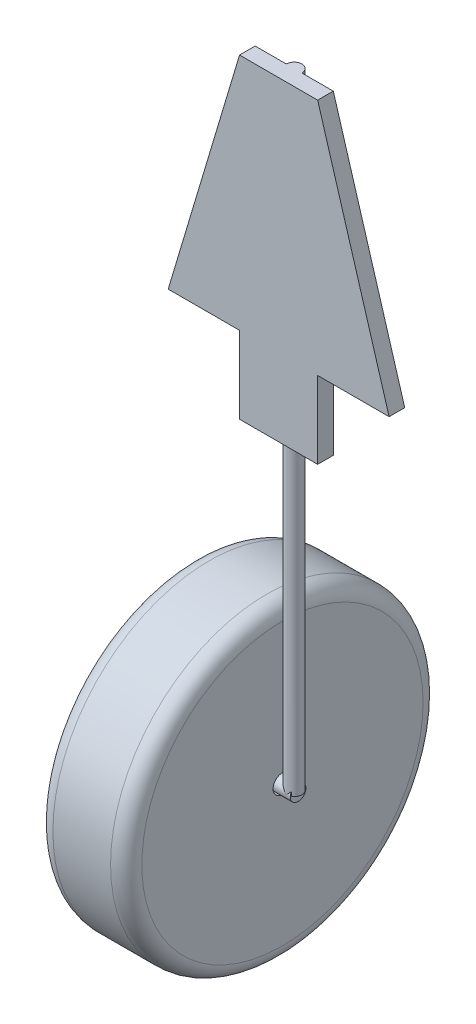
SolidWorks part; units mm, degrees
material "Silicon Rubber"
ref_plane "Front Plane" through (0, 0, 0) normal (0, 0, 1) x (1, 0, 0)
ref_plane "Top Plane" through (0, 0, 0) normal (0, 1, 0) x (1, 0, 0)
ref_plane "Right Plane" through (0, 0, 0) normal (1, 0, 0) x (0, 0, -1)
sketch "Sketch1" plane through (0, 0, 0) normal (1, 0, 0) x (0, 0, -1)
  circle A0 centre (0, 0) radius 10
  circle A1 centre (0, 0) radius 0.6
  dimension "D1" = 20
  dimension "D2" = 1.2
extrude "Boss-Extrude1" add sketch "Sketch1" along normal blind 5.69
fillet "Fillet2" radius 1 1 edges at (0, 0, -10)
fillet "Fillet3" radius 1 1 edges at (5.69, 0, -10)
sketch "Sketch2" plane through (5.69, 0, 0) normal (1, 0, 0) x (0, 0, -1)
  circle A0 centre (0, 0) radius 0.5
  dimension "D1" = 1
extrude "Boss-Extrude2" add sketch "Sketch2" along normal blind 1 and the other way blind 6 separate body
sketch "Sketch4" plane through (0, 0, 0) normal (0, 1, 0) x (1, 0, 0)
  line L0 (9.1493, 0) -> (0, 0) construction
  circle A0 centre (6.4348, 0) radius 0.5
  dimension "D1" = 1
extrude "Boss-Extrude5" add sketch "Sketch4" along normal blind 40
sketch "Sketch14" plane through (0, 0, 0) normal (0, 0, 1) x (1, 0, 0)
  line L5 (6.4348, 40) -> (6.4348, 5.6979) construction
  line L6 (6.9348, 40) -> (5.9348, 40) construction
  line L7 (8.9428, 40) -> (3.9428, 40)
  line L8 (3.9428, 19.814) -> (8.9428, 19.814)
  line L9 (8.9428, 19.814) -> (8.9428, 24.742)
  line L10 (8.9428, 24.742) -> (13.516, 24.742)
  line L11 (13.516, 24.742) -> (8.9428, 40)
  line L12 (3.9428, 19.814) -> (3.9428, 24.742)
  line L13 (3.9428, 24.742) -> (-0.6232, 24.742)
  line L14 (-0.6232, 24.742) -> (3.9428, 40)
  point P7 (6.4428, 40)
  dimension "D1" = 5
  dimension "D2" = 3.9428
  dimension "D3" = 19.814
  dimension "D4" = 13.516
  dimension "D5" = 0.6232
  dimension "D6" = 24.742
extrude "Boss-Extrude8" add sketch "Sketch14" along normal blind 1
